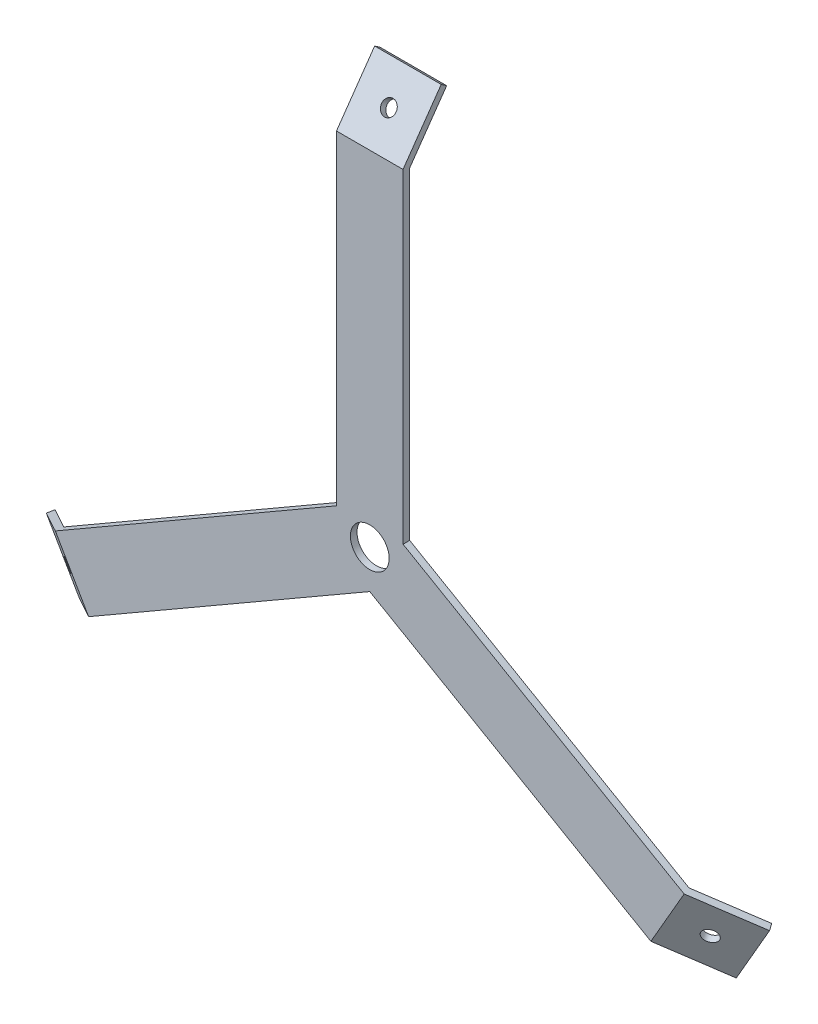
SolidWorks part; units mm, degrees
ref_plane "Спереди" through (0, 0, 0) normal (0, 0, 1) x (1, 0, 0)
ref_plane "Сверху" through (0, 0, 0) normal (0, 1, 0) x (1, 0, 0)
ref_plane "Справа" through (0, 0, 0) normal (1, 0, 0) x (0, 0, -1)
sketch "Эскиз1" plane through (0, 0, 0) normal (1, 0, 0) x (0, 0, -1)
  line L0 (0, 0) -> (0, 155)
  line L1 (0, 155) -> (17.2073, 179.5746)
  line L2 (0, 0) -> (50000, 0) construction
  dimension "D1" = 145
  dimension "D2" = 155
  dimension "D3" = 30
extrude "Вытянуть-Тонкостенный1" add sketch "Эскиз1" along normal blind 15 and the other way blind 15 thin thin type one direction wall 3
ref_axis "Ось1" through (0, 0, 0) along (0, 0, -1)
pattern_circular "Круговой массив1" count 3 over 360 about axis through (0, 0, 0) along (0, 0, -1) of "Вытянуть-Тонкостенный1"
hole_wizard "Отверстие с зазором M161" positions "Эскиз3" profile "Эскиз5" hole size "M16" standard "ISO" end condition through all
sketch "Эскиз3" plane through (0, 0, -3) normal (0, 0, -1) x (-1, 0, 0)
  point P0 (0, 0)
sketch "Эскиз5" plane through (0, 0, -3) normal (1, 0, 0) x (0, 1, 0)
  line L0 (0, 0) -> (0, 3)
  line L1 (0, 3) -> (8.75, 3)
  line L2 (8.75, 3) -> (8.75, 0)
  line L5 (8.75, 0) -> (0, 0)
  line L11 (0, -6.35) -> (0, 107.95) construction
  dimension "Диаметр сквозного отверстия" = 17.5
  dimension "Глубина сквозного отверстия" = 3
ref_plane "Плоскость1" through (0, 49.2727, 70.3687) normal (0, -0.5736, -0.8192) x (-1, 0, 0)
sketch "Эскиз7" plane through (0, 49.2727, 70.3687) normal (0, -0.5736, -0.8192) x (-1, 0, 0)
  point P0 (0, 141.9686)
  dimension "D1" = 15
  dimension "D2" = 15
hole_wizard "Отверстие с зазором M62" positions "Трехмерный эскиз3" profile "Эскиз8" hole size "M6" standard "ISO" end condition through all
sketch3d "Трехмерный эскиз3"
  point P0 (0, 165.5666, -11.0611)
sketch "Эскиз8" plane through (0, 165.5666, -11.0611) normal (1, 0, 0) x (0, 0.8192, -0.5736)
  line L0 (0, 0) -> (0, 24.5464)
  line L1 (0, 24.5464) -> (3.3, 24.5464)
  line L2 (3.3, 24.5464) -> (3.3, 0)
  line L5 (3.3, 0) -> (0, 0)
  line L11 (0, -6.35) -> (0, 107.95) construction
  dimension "Диаметр сквозного отверстия" = 6.6
  dimension "Глубина сквозного отверстия" = 24.5464
pattern_circular "Круговой массив2" count 3 every 120 about axis through (0, 0, 0) along (0, 0, -1) of "Отверстие с зазором M62"
